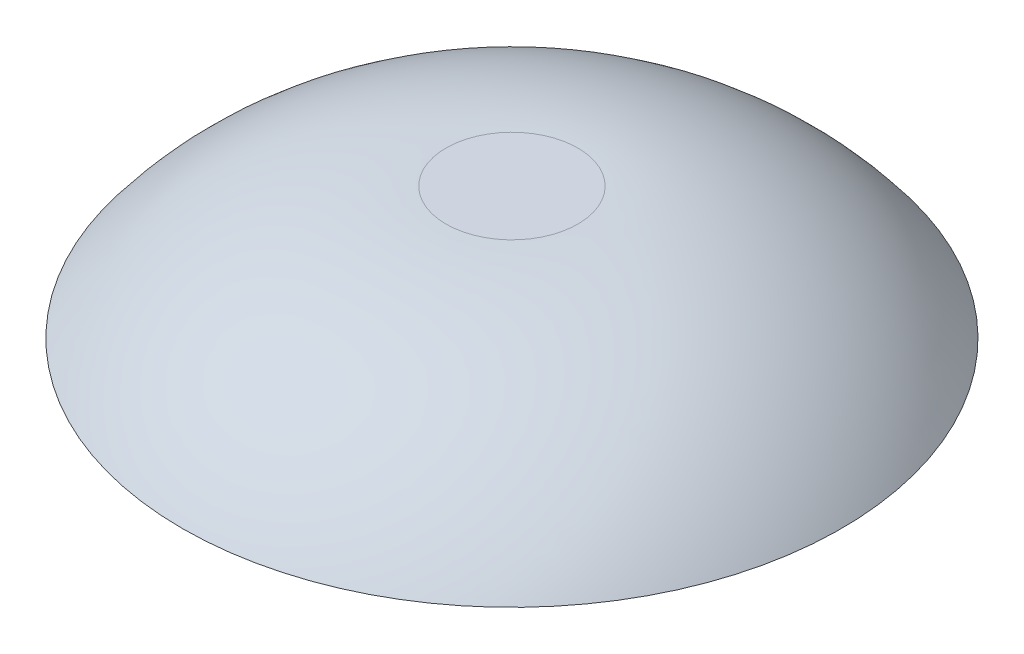
SolidWorks part; units mm, degrees
ref_plane "Front Plane" through (0, 0, 0) normal (0, 0, 1) x (1, 0, 0)
ref_plane "Top Plane" through (0, 0, 0) normal (0, 1, 0) x (1, 0, 0)
ref_plane "Right Plane" through (0, 0, 0) normal (1, 0, 0) x (0, 0, -1)
sketch "Sketch1" plane through (0, 0, 0) normal (0, 1, 0) x (1, 0, 0)
  circle A0 centre (0, 0) radius 25
  dimension "D1" = 50
extrude "Boss-Extrude1" add sketch "Sketch1" along normal blind 10
fillet "Fillet1" radius 25 1 edges at (0, 10, 25)
